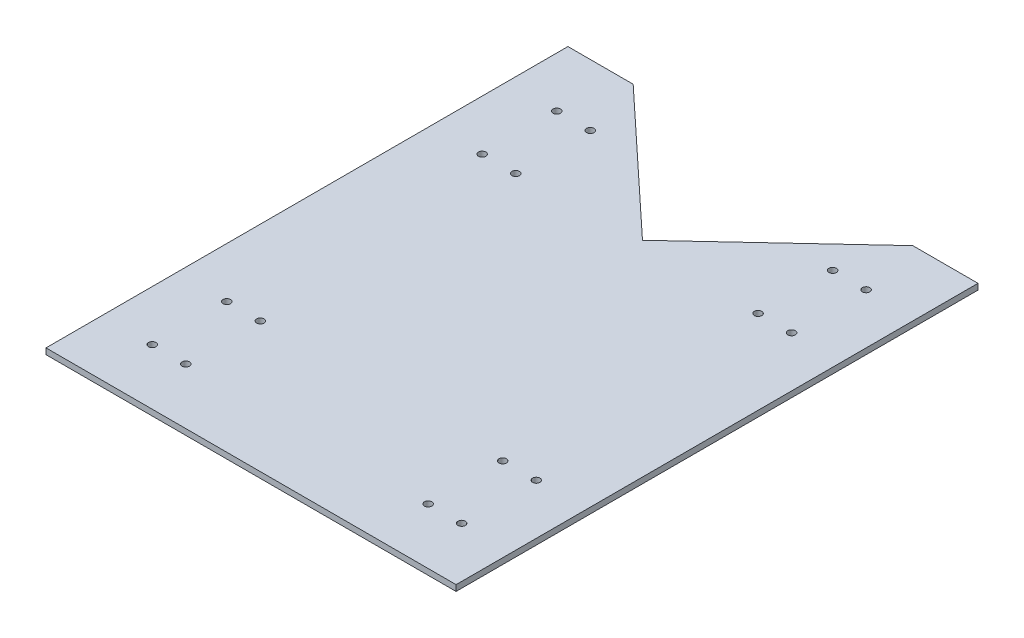
SolidWorks part; units mm, degrees
material "ABS"
ref_plane "Front Plane" through (0, 0, 0) normal (0, 0, 1) x (1, 0, 0)
ref_plane "Top Plane" through (0, 0, 0) normal (0, 1, 0) x (1, 0, 0)
ref_plane "Right Plane" through (0, 0, 0) normal (1, 0, 0) x (0, 0, -1)
sketch "Sketch3" plane through (0, 0, 0) normal (0, 1, 0) x (1, 0, 0)
  line L1 (-110, -140) -> (110, -140)
  line L2 (-110, -140) -> (-110, 140)
  line L3 (-110, 140) -> (110, 140)
  line L4 (110, -140) -> (110, 140)
  line L5 (-110, -140) -> (110, 140) construction
  line L6 (-110, 140) -> (110, -140) construction
  point P0 (0, 0)
  dimension "D1" = 220
  dimension "D2" = 280
extrude "Boss-Extrude1" add sketch "Sketch3" along normal blind 3.175
sketch "Sketch4" plane through (0, 3.175, 0) normal (0, 1, 0) x (1, 0, 0)
  line L0 (110, -140) -> (110, 140) construction
  line L1 (110, -140) -> (100, -140)
  line L2 (110, -140) -> (110, -130)
  line L3 (110, -65) -> (100, -65)
  line L4 (35, -140) -> (35, -130)
  line L5 (-110, -140) -> (110, -140) construction
  line L6 (45, -140) -> (45, -130)
  line L7 (100, -65) -> (100, -75)
  line L8 (45, -65) -> (35, -65)
  line L9 (45, -140) -> (35, -140)
  line L10 (35, -130) -> (45, -130)
  line L11 (35, -75) -> (45, -75)
  line L12 (100, -75) -> (110, -75)
  line L13 (100, -130) -> (110, -130)
  line L14 (35, -75) -> (35, -65)
  line L15 (45, -75) -> (45, -65)
  line L16 (100, -130) -> (100, -140)
  line L17 (110, -75) -> (110, -65)
  point P20 (105, -130)
  dimension "D1" = 0
  dimension "D2" = 0
  dimension "D3" = 75
  dimension "D4" = 75
  dimension "D5" = 10
  dimension "D6" = 10
  dimension "D7" = 10
  dimension "D8" = 10
  dimension "D9" = 10
extrude "Boss-Extrude2" [suppressed] add sketch "Sketch4" along normal blind 50
sketch "Sketch7" plane through (0, 0, 0) normal (0, -1, 0) x (1, 0, 0)
  line L0 (110, 140) -> (110, -140) construction
  line L1 (-110, 140) -> (110, 140) construction
  line L2 (110, -140) -> (-110, -140) construction
  line L3 (0, 0) -> (0, -140) construction
  line L4 (-83, 70) -> (83, 70) construction
  line L5 (-83, 110) -> (83, 110) construction
  line L6 (-110, -140) -> (-110, 140) construction
  line L7 (-65, 110) -> (-65, 140) construction
  line L8 (-65, 110) -> (-65, 70) construction
  line L9 (-83, 110) -> (-83, 70) construction
  line L10 (83, 70) -> (83, 110) construction
  line L11 (65, 110) -> (65, 70) construction
  circle A8 centre (-83, 70) radius 2
  circle A9 centre (-83, 110) radius 2
  circle A10 centre (-65, 110) radius 2
  circle A11 centre (-65, 70) radius 2
  circle A12 centre (65, 110) radius 2
  circle A13 centre (83, 110) radius 2
  circle A14 centre (83, 70) radius 2
  circle A15 centre (65, 70) radius 2
  circle A16 centre (83, -107) radius 2
  circle A17 centre (65, -67) radius 2
  circle A18 centre (83, -67) radius 2
  circle A19 centre (65, -107) radius 2
  circle A20 centre (-65, -107) radius 2
  circle A21 centre (-83, -107) radius 2
  circle A22 centre (-83, -67) radius 2
  circle A23 centre (-65, -67) radius 2
  dimension "D12" = 40
  dimension "D4" = 27
  dimension "D3" = 18
  dimension "D5" = 40
  dimension "D6" = 40
  dimension "D7" = 18
  dimension "D8" = 27
  dimension "D9" = 33
  dimension "D10" = 18
  dimension "D11" = 40
  dimension "D13" = 40
  dimension "D16" = 27
  dimension "D27" = 30
extrude "Cut-Extrude2" cut sketch "Sketch7" against normal blind 10
sketch "Sketch8" plane through (0, 3.175, 0) normal (0, 1, 0) x (1, 0, 0)
  line L0 (-110, -140) -> (110, -140) construction
  line L1 (-110, 140) -> (-110, -140) construction
  line L2 (110, -140) -> (110, 140) construction
  circle A0 centre (-45, -35) radius 4
  circle A1 centre (-25, -35) radius 4
  circle A5 centre (-45, 40) radius 4
  circle A6 centre (-25, 40) radius 4
  circle A7 centre (55, 2.5) radius 4
  circle A8 centre (75, 2.5) radius 4
  dimension "D1" = 8
  dimension "D2" = 8
  dimension "D4" = 8
  dimension "D5" = 8
  dimension "D7" = 8
  dimension "D8" = 8
  dimension "D3" = 20
  dimension "D6" = 20
  dimension "D9" = 20
  dimension "D10" = 105
  dimension "D11" = 65
  dimension "D12" = 65
  dimension "D13" = 75
  dimension "D14" = 37.5
  dimension "D15" = 35
extrude "Cut-Extrude3" [suppressed] cut sketch "Sketch8" against normal blind 10
sketch "Sketch9" plane through (0, 3.175, 0) normal (0, 1, 0) x (1, 0, 0)
  line L5 (50, 98.4245) -> (110, 98.4245) construction
  line L6 (110, -140) -> (110, 140) construction
  line L7 (-50, 98.4245) -> (-110, 98.4245) construction
  line L8 (-110, 140) -> (-110, -140) construction
  line L13 (-110, 70) -> (110, 70) construction
  line L14 (0, 70) -> (75, 140)
  line L15 (110, 140) -> (-110, 140) construction
  line L16 (75, 140) -> (-75, 140)
  line L17 (-75, 140) -> (0, 70)
  line L18 (0, 70) -> (0, 140) construction
  dimension "D1" = 150
  dimension "D2" = 35
  dimension "D3" = 70
extrude "Cut-Extrude4" cut sketch "Sketch9" against normal blind 10
